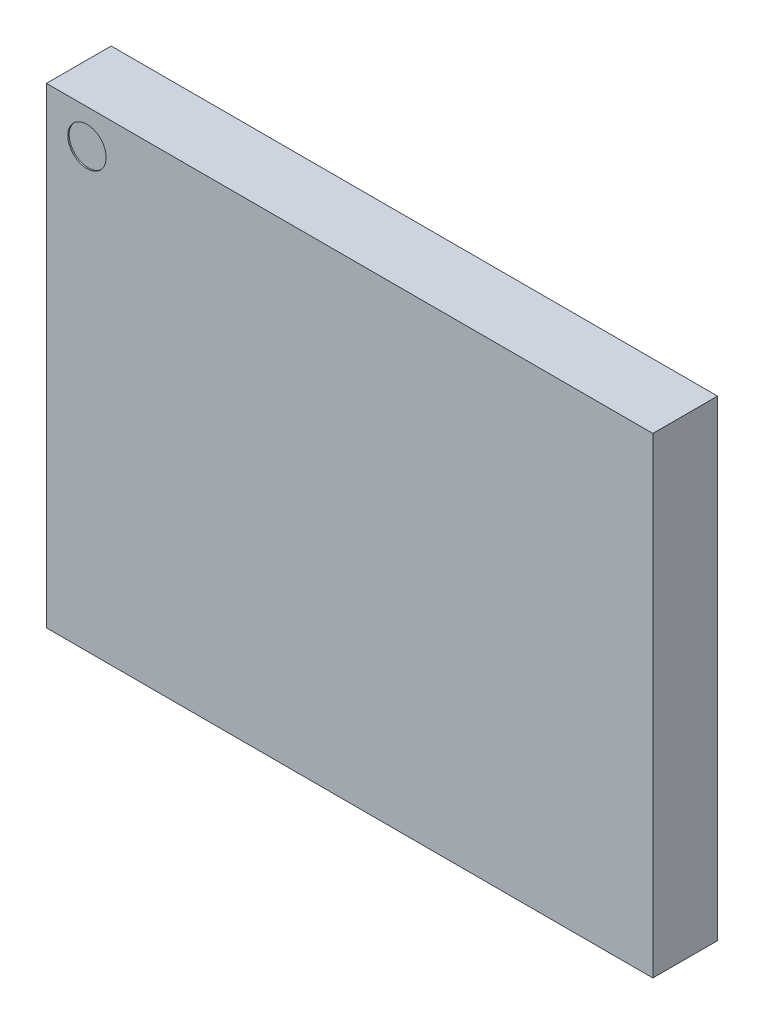
SolidWorks part; units mm, degrees
ref_plane "Front Plane" through (0, 0, 0) normal (0, 0, 1) x (1, 0, 0)
ref_plane "Top Plane" through (0, 0, 0) normal (0, 1, 0) x (1, 0, 0)
ref_plane "Right Plane" through (0, 0, 0) normal (1, 0, 0) x (0, 0, -1)
sketch "Sketch1" plane through (0, 0, 0) normal (0, 0, 1) x (1, 0, 0)
  line L1 (-4.5, -3.5) -> (4.5, -3.5)
  line L2 (-4.5, -3.5) -> (-4.5, 3.5)
  line L3 (-4.5, 3.5) -> (4.5, 3.5)
  line L4 (4.5, -3.5) -> (4.5, 3.5)
  line L5 (-4.5, -3.5) -> (4.5, 3.5) construction
  line L6 (-4.5, 3.5) -> (4.5, -3.5) construction
  point P0 (0, 0)
  dimension "D1" = 9
  dimension "D2" = 7
extrude "Boss-Extrude1" add sketch "Sketch1" along normal blind 0.96
ref_plane "Plane1" through (0, 3, 0) normal (0, 1, 0) x (1, 0, 0)
sketch "Sketch3" plane through (0, 3, 0) normal (0, 1, 0) x (1, 0, 0)
  line L0 (4.5, 0) -> (-4.5, 0) construction
  line L1 (4.09, 0) -> (3.91, 0)
  line L2 (4, 0) -> (4, 0.5238) construction
  arc A0 (4.09, 0) -> (3.91, 0) centre (4, 0.12) ccw
  dimension "D1" = 0.3
  dimension "D2" = 0.12
  dimension "D3" = 0.5
revolve "Revolve1" add sketch "Sketch3" angle 360 about L2 region at (4.0653, 3, -0.1273)
pattern_linear "LPattern1" count 17 spacing 0.5 along (-1, 0, 0) count 13 spacing 0.5 along (0, -1, 0) skipping (2, 2), (2, 3), (2, 4), (2, 5), (2, 6), (2, 7), (2, 8), (2, 9), (2, 10), (3, 2), (3, 3), (3, 4), (3, 5), (3, 6), (3, 7), (3, 8), (3, 9), (3, 10), (4, 2), (4, 3), (4, 4), (4, 5), (4, 6), (4, 7), (4, 8), (4, 9), (4, 10), (5, 2), (5, 3), (5, 4), (5, 5), (5, 6), (5, 7), (5, 8), (5, 9), (5, 10), (6, 2), (6, 3), (6, 4), (6, 5), (6, 6), (6, 7), (6, 8), (6, 9), (6, 10), (7, 2), (7, 3), (7, 4), (7, 5), (7, 6), (7, 7), (7, 8), (7, 9), (7, 10), (8, 2), (8, 3), (8, 4), (8, 5), (8, 6), (8, 7), (8, 8), (8, 9), (8, 10), (9, 2), (9, 3), (9, 4), (9, 5), (9, 6), (9, 7), (9, 8), (9, 9), (9, 10), (10, 2), (10, 3), (10, 4), (10, 5), (10, 6), (10, 7), (10, 8), (10, 9), (10, 10), (11, 2), (11, 3), (11, 4), (11, 5), (11, 6), (11, 7), (11, 8), (11, 9), (11, 10), (12, 2), (12, 3), (12, 4), (12, 5), (12, 6), (12, 7), (12, 8), (12, 9), (12, 10), (13, 2), (13, 3), (13, 4), (13, 5), (13, 6), (13, 7), (13, 8), (13, 9), (13, 10), (14, 2), (14, 3), (14, 4), (14, 5), (14, 6), (14, 7), (14, 8), (14, 9), (14, 10) of "Revolve1"
sketch "Sketch4" plane through (0, 0, 0.96) normal (0, 0, 1) x (1, 0, 0)
  circle A0 centre (-3.8988, 2.989) radius 0.2847
extrude "Cut-Extrude1" cut sketch "Sketch4" against normal blind 0.02
